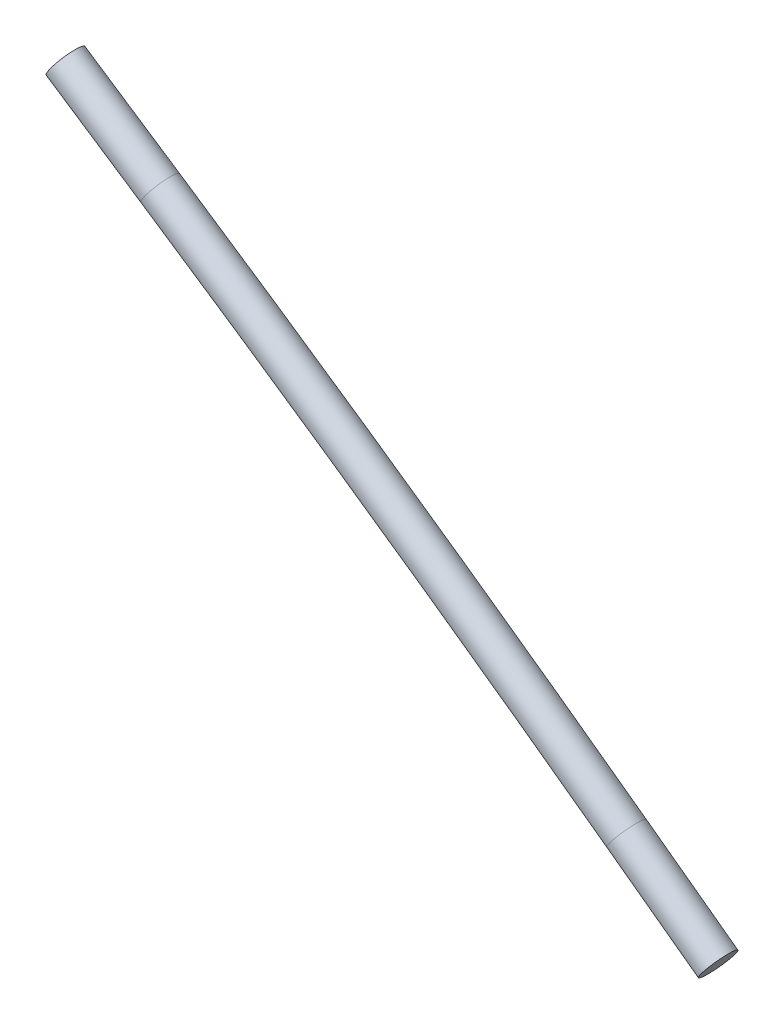
SolidWorks part; units mm, degrees
material "Aço cromo inoxidável"
ref_plane "Plano frontal" through (0, 0, 0) normal (0, 0, 1) x (1, 0, 0)
ref_plane "Plano superior" through (0, 0, 0) normal (0, 1, 0) x (1, 0, 0)
ref_plane "Plano direito" through (0, 0, 0) normal (1, 0, 0) x (0, 0, -1)
sketch "Esboço1" plane through (0, 0, 0) normal (0, 0, 1) x (1, 0, 0)
  line L0 (-28.7425, 234.7519) -> (-45.4104, 245.8055)
  line L1 (-30.7155, 231.7767) -> (-26.7694, 237.7272) construction
  line L2 (53.2373, 177.4867) -> (69.3518, 165.6409)
  line L4 (-18.2369, 231.352) -> (-21.5704, 226.3632) construction
  line L6 (-47.0684, 243.3054) -> (-43.7523, 248.3057) construction
  arc A2 (-28.7425, 234.7519) -> (53.2373, 177.4867) centre (-1172.5398, -1489.9985) cw
  point P2 (-19.9036, 228.8576)
  dimension "D1" = 100
  dimension "D2" = 20
sweep "Varredura1" add path "Esboço1" circular profile diameter 6 parameters "D3"=6
chamfer "Chanfro1" [suppressed] distance 0.5 angle 45
